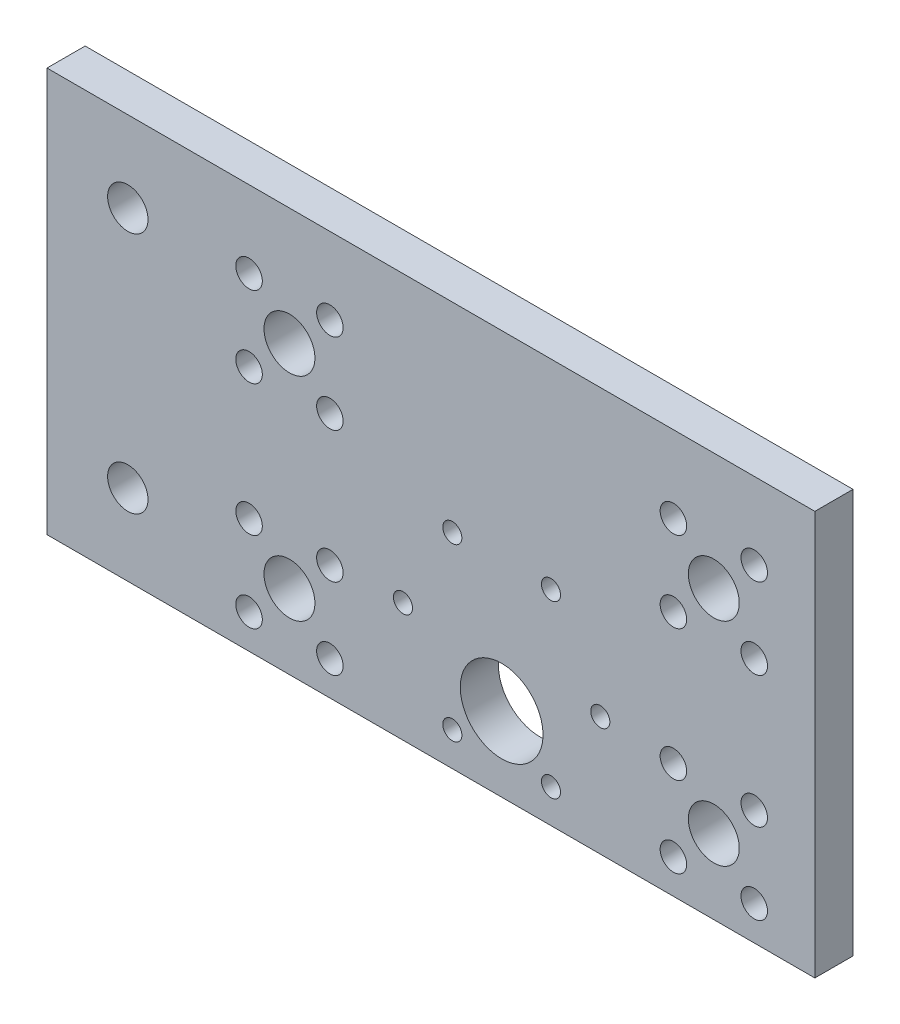
SolidWorks part; units mm, degrees
ref_plane "Front Plane" through (0, 0, 0) normal (0, 0, 1) x (1, 0, 0)
ref_plane "Top Plane" through (0, 0, 0) normal (0, 1, 0) x (1, 0, 0)
ref_plane "Right Plane" through (0, 0, 0) normal (1, 0, 0) x (0, 0, -1)
sketch "Sketch1" plane through (0, 0, 0) normal (0, 0, 1) x (1, 0, 0)
  line L0 (12.7, 63.5) -> (12.7, 0) construction
  line L1 (0, 0) -> (120.65, 0)
  line L2 (0, 0) -> (0, 63.5)
  line L3 (0, 63.5) -> (120.65, 63.5)
  line L4 (120.65, 0) -> (120.65, 63.5)
  line L5 (55.9375, 18.7206) -> (71.4375, 18.7206) construction
  line L6 (71.4375, 18.7206) -> (80.6875, 34.7421) construction
  line L7 (71.4375, 18.7206) -> (80.6875, 2.6992) construction
  line L8 (71.4375, 18.7206) -> (86.9375, 18.7206) construction
  circle A0 centre (71.4375, 11.7206) radius 6.5
  circle A1 centre (71.4375, 18.7206) radius 18.5 construction
  circle A2 centre (55.9375, 18.7206) radius 1.5
  circle A3 centre (86.9375, 18.7206) radius 1.5
  circle A4 centre (79.1875, 5.2972) radius 1.5
  circle A5 centre (63.6875, 5.2972) radius 1.5
  circle A6 centre (63.6875, 32.144) radius 1.5
  circle A7 centre (79.1875, 32.144) radius 1.5
  circle A8 centre (71.4375, 18.7206) radius 15.5 construction
  circle A9 centre (38.1, 45.0708) radius 4
  circle A10 centre (12.7, 50.8) radius 3.175
  circle A11 centre (12.7, 12.7) radius 3.175
  circle A12 centre (104.775, 45.0708) radius 4
  circle A13 centre (104.775, 11.7206) radius 4
  circle A14 centre (38.1, 11.7206) radius 4
  circle A15 centre (31.75, 18.0706) radius 2.0828
  circle A16 centre (31.75, 5.3706) radius 2.0828
  circle A17 centre (44.45, 5.3706) radius 2.0828
  circle A18 centre (44.45, 18.0706) radius 2.0828
  circle A19 centre (31.75, 51.4208) radius 2.0828
  circle A20 centre (31.75, 38.7208) radius 2.0828
  circle A21 centre (44.45, 38.7208) radius 2.0828
  circle A22 centre (44.45, 51.4208) radius 2.0828
  circle A23 centre (98.425, 51.4208) radius 2.0828
  circle A24 centre (98.425, 38.7208) radius 2.0828
  circle A25 centre (111.125, 38.7208) radius 2.0828
  circle A26 centre (111.125, 51.4208) radius 2.0828
  circle A31 centre (98.425, 18.0706) radius 2.0828
  circle A32 centre (98.425, 5.3706) radius 2.0828
  circle A33 centre (111.125, 5.3706) radius 2.0828
  circle A34 centre (111.125, 18.0706) radius 2.0828
  dimension "D3" = 13
  dimension "D4" = 37
  dimension "D7" = 3
  dimension "D10" = 8
  dimension "D12" = 15.5
  dimension "D15" = 7.75
  dimension "D8" = 31
  dimension "D14" = 31
  dimension "D17" = 66.675
  dimension "D20" = 4.1656
  dimension "D25" = 6.35
  dimension "D26" = 12.7
  dimension "D27" = 12.7
  dimension "D33" = 4.1656
  dimension "D34" = 4.1656
  dimension "D39" = 4.1656
  dimension "D1" = 120.65
  dimension "D5" = 7
  dimension "D6" = 33.3375
  dimension "D9" = 120
  dimension "D11" = 60
  dimension "D13" = 63.5
  dimension "D16" = 11.7206
  dimension "D18" = 6.35
  dimension "D19" = 33.3502
  dimension "D21" = 12.7
  dimension "D22" = 12.7
  dimension "D23" = 12.7
  dimension "D24" = 6.35
  dimension "D28" = 38.1
  dimension "D29" = 12.7
  dimension "D30" = 6.35
  dimension "D31" = 12.7
  dimension "D32" = 6.35
  dimension "D35" = 12.7
  dimension "D36" = 6.35
  dimension "D37" = 6.35
  dimension "D38" = 12.7
  dimension "D40" = 12.7
  dimension "D41" = 12.7
  dimension "D42" = 6.35
  dimension "D43" = 6.35
extrude "Boss-Extrude1" add sketch "Sketch1" along normal blind 5.9944
